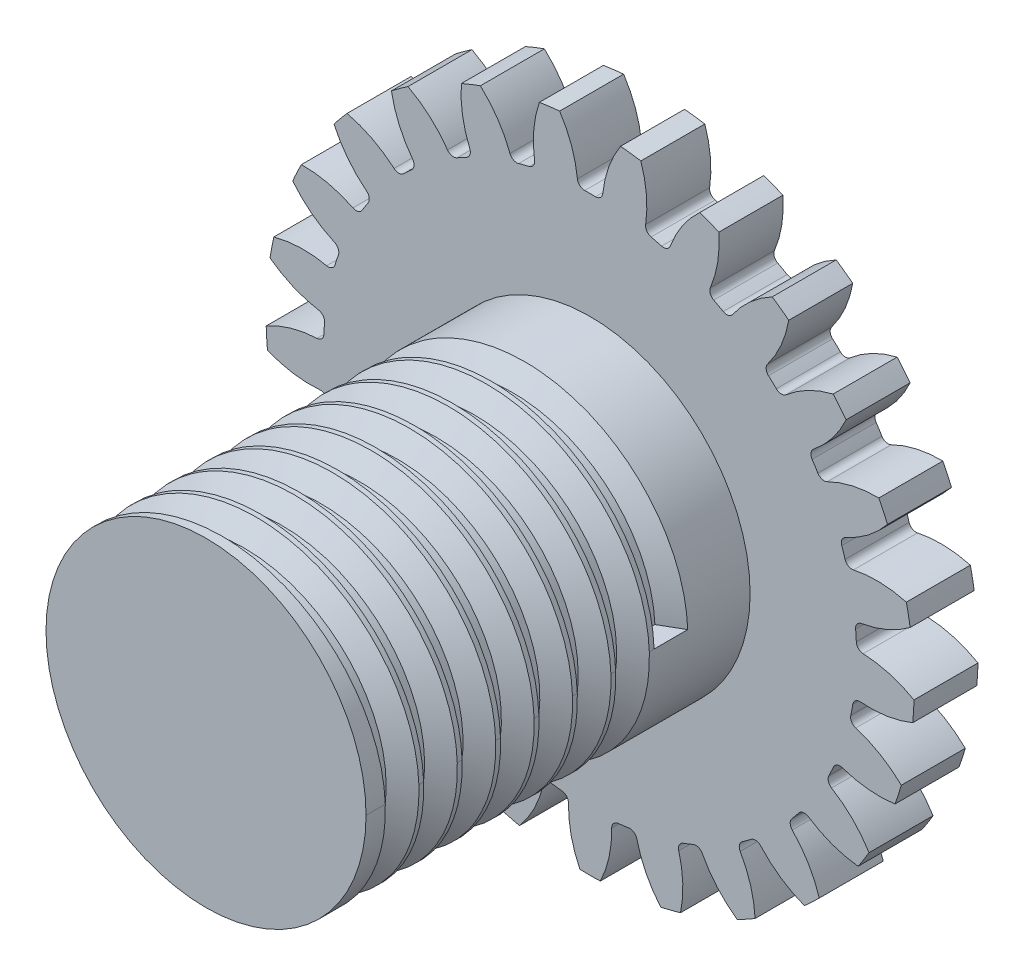
SolidWorks part; units mm, degrees
material "Plain Carbon Steel"
ref_plane "Front Plane" through (0, 0, 0) normal (0, 0, 1) x (1, 0, 0)
ref_plane "Top Plane" through (0, 0, 0) normal (0, 1, 0) x (1, 0, 0)
ref_plane "Right Plane" through (0, 0, 0) normal (1, 0, 0) x (0, 0, -1)
sketch "Sketch1" plane through (0, 0, 0) normal (0, 0, 1) x (1, 0, 0)
  circle A0 centre (0, 0) radius 4.6875
  circle A1 centre (0, 0) radius 5.0625
  circle A2 centre (0, 0) radius 4.1625
  dimension "D1" = 9.375
  dimension "D2" = 10.125
  dimension "D3" = 0.9
extrude "Boss-Extrude1" add sketch "Sketch1" along normal mid plane 1 contours A1
sketch "Sketch2" plane through (0, 0, 0) normal (0, 0, 1) x (1, 0, 0)
  line L0 (0, 0) -> (0, 5.0625) construction
  line L1 (-0.2943, 4.6783) -> (0.2943, 4.6783) construction
  line L2 (-0.1903, 4.1581) -> (0, 0) construction
  line L3 (0, 3.8696) -> (-0.7798, 6.0121) construction
  line L4 (0, 0) -> (0.6345, 5.0226) construction
  line L5 (0.2943, 4.6783) -> (0.8783, 4.6045) construction
  circle A0 centre (0, 0) radius 5.0625 construction
  arc A1 (-1.7071, 5.8172) -> (-0.1903, 4.1581) centre (-1.9438, 4.0779) cw
  circle A3 centre (0, 0) radius 4.1625 construction
  arc A7 (1.7071, 5.8172) -> (0.1903, 4.1581) centre (1.9438, 4.0779) ccw
  arc A8 (0.1903, 4.1581) -> (-0.1903, 4.1581) centre (0, 0) ccw
  circle A10 centre (0, 0) radius 4.6875 construction
  circle A11 centre (0, 0) radius 6.0625
  arc A12 (1.7071, 5.8172) -> (-1.7071, 5.8172) centre (0, 0) ccw
  circle A13 centre (0, 0) radius 5.0625 construction
  dimension "D2" = 20
  dimension "D3" = 7.2
extrude "Cut-Extrude1" cut sketch "Sketch2" against normal through all both and the other way through all
fillet "Fillet1" radius 0.1125 2 edges at (0.1903, 4.1581, 0) (-0.1903, 4.1581, 0)
pattern_circular "CirPattern1" count 25 over 360 about axis through (0, 0, 0.5) along (0, 0, 1) of "Fillet1", "Cut-Extrude1"
sketch "Sketch3" plane through (0, 0, -0.5) normal (0, 0, -1) x (-1, 0, 0)
  circle A0 centre (0, 0) radius 1.1719
  dimension "D1" = 2.3438
extrude "Nominal Shaft Diameter" cut sketch "Sketch3" against normal through all
sketch "Sketch4" plane through (0, 0, 0.5) normal (0, 0, 1) x (1, 0, 0)
  line L1 (0.3662, 1.5381) -> (-0.3662, 1.5381)
  line L2 (0.3662, 1.5381) -> (0.3662, 0.8057)
  line L3 (0.3662, 0.8057) -> (-0.3662, 0.8057)
  line L4 (-0.3662, 1.5381) -> (-0.3662, 0.8057)
  line L5 (0.3662, 1.5381) -> (-0.3662, 0.8057) construction
  line L6 (0.3662, 0.8057) -> (-0.3662, 1.5381) construction
  circle A1 centre (0, 0) radius 1.1719
  point P3 (0, 1.1719)
  dimension "D2" = 2.3438
  dimension "D1" = 0.7324
extrude "Keyway" [suppressed] cut sketch "Sketch4" against normal through all contours A1 L2 L1 L4
sketch "Sketch5" plane through (0, 0, 0.5) normal (0, 0, 1) x (1, 0, 0)
  circle A0 centre (0, 0) radius 2.5
  circle A2 centre (0, 0) radius 1.1719 construction
  circle A3 centre (0, 0) radius 1.1719
  dimension "D1" = 5
extrude "Boss-Extrude2" add sketch "Sketch5" along normal blind 6 contours A0
extrude "Boss-Extrude3" add sketch "Sketch5<3>" against normal up to surface (1 mm away) contours A3 up to face at (-1.1719, 0, -0.5)
sketch "Sketch5<3>" plane through (0, 0, 0.5) normal (0, 0, 1) x (1, 0, 0) same geometry as "Sketch5"
thread "Thread1" pitch 0.6 method cut profile "Thread Profile1" start angle 0, offset 0, length 4.5, pitch 0.6, diameter 5
ref_plane "Plane1" through (-2.5, 0, 6.5) normal (0, -1, 0) x (-1, 0, 0)
sketch "Thread Profile1" plane through (-2.5, 0, 6.5) normal (0, -1, 0) x (-1, 0, 0)
  line L0 (0, 0) -> (0, 0.6) construction
  line L11 (0, 0) -> (0, 0.525)
  line L12 (0, 0.525) -> (-0.3248, 0.3375)
  line L13 (-0.3248, 0.3375) -> (-0.3248, 0.1875)
  line L15 (-0.3248, 0.1875) -> (0, 0)
  line L17 (-0.3248, 0.2625) -> (0, 0.2625) construction
  point P2 (0, 0)
  dimension "Pitch" = 0.6
  dimension "Profile_Angle" = 60
  dimension "Profile_Land" = 0.15
  dimension "Profile_Height" = 0.3248
equation "\"Module\"= .375"
equation "\"Number of Teeth\"= 25"
equation "\"D1@Sketch1\"=\"Module\" *\"Number of Teeth\""
equation "\"D2@Sketch1\"=(\"Number of Teeth\" +2) * \"Module\""
equation "\"D3@Sketch1\"=\"Module\" * if( \"Module\" =>1.25, 2.25,2.4)"
equation "\"D3@Sketch2\"=180 / \"Number of Teeth\""
equation "\"D1@Fillet1\"=.3 * \"Module\""
equation "\"D1@CirPattern1\"=\"Number of Teeth\""
equation "\"NSD\"= ( \"Module\" * \"Number of Teeth\" ) / 4"
equation "\"Key way\"= \"NSD\" / 3.2"
equation "\"D1@Sketch4\"=\"Key way\""
equation "\"D2@Sketch4\"=\"NSD\""
equation "\"D1@Sketch3\"=\"NSD\""
equation "\"face width\"= 1"
equation "\"D1@Boss-Extrude1\"=\"face width\""
